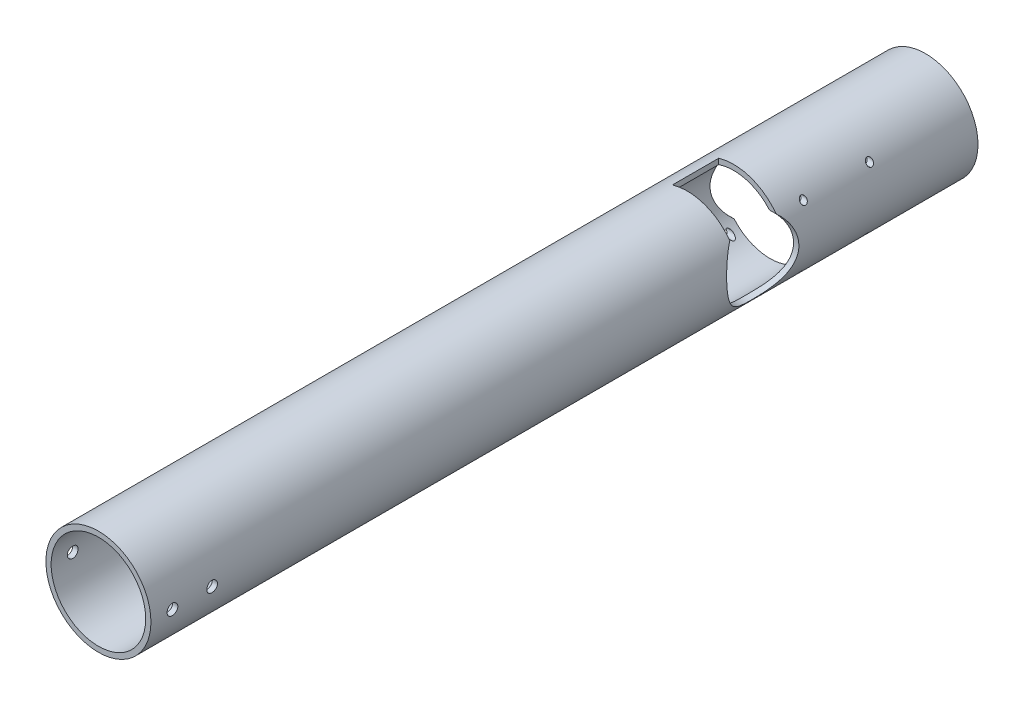
SolidWorks part; units mm, degrees
ref_plane "Front Plane" through (0, 0, 0) normal (0, 0, 1) x (1, 0, 0)
ref_plane "Top Plane" through (0, 0, 0) normal (0, 1, 0) x (1, 0, 0)
ref_plane "Right Plane" through (0, 0, 0) normal (1, 0, 0) x (0, 0, -1)
sketch "Sketch1" plane through (0, 0, 0) normal (0, 0, 1) x (1, 0, 0)
  circle A0 centre (0, 0) radius 31.75
  circle A1 centre (0, 0) radius 28.575
  dimension "D1" = 63.5
  dimension "D2" = 57.15
extrude "Boss-Extrude1" add sketch "Sketch1" along normal blind 250 and the other way blind 250 contours A1 | A0 region at (0, 0, 0)
sketch "Sketch2" plane through (0, 0, 0) normal (1, 0, 0) x (0, 0, -1)
  circle A2 centre (170, -2) radius 21.75
  dimension "D1" = 43.5
  dimension "D2" = 170
  dimension "D3" = 2
extrude "Cut-Extrude1" cut sketch "Sketch2" against normal through all
sketch "Sketch3" plane through (0, 0, 0) normal (1, 0, 0) x (0, 0, -1)
  circle A1 centre (120, 2) radius 21.75
  dimension "D1" = 120
  dimension "D2" = 43.5
  dimension "D3" = 2
extrude "Cut-Extrude2" cut sketch "Sketch3" along normal through all
sketch "Sketch5" plane through (0, 0, 0) normal (1, 0, 0) x (0, 0, -1)
  line L1 (184, -12.75) -> (156, -12.75)
  line L2 (184, -12.75) -> (184, -34.75)
  line L3 (184, -34.75) -> (156, -34.75)
  line L4 (156, -12.75) -> (156, -34.75)
  line L5 (184, -12.75) -> (156, -34.75) construction
  line L6 (184, -34.75) -> (156, -12.75) construction
  circle A0 centre (170, -2) radius 21.75 construction
  circle A1 centre (170, -2) radius 21.75 construction
  point P0 (170, -23.75)
  dimension "D1" = 28
  dimension "D2" = 22
  dimension "D3" = 170
extrude "Cut-Extrude4" cut sketch "Sketch5" against normal through all from offset 9
sketch "Sketch6" plane through (0, 0, 0) normal (1, 0, 0) x (0, 0, -1)
  line L1 (106, 34.75) -> (134, 34.75)
  line L2 (106, 34.75) -> (106, 12.75)
  line L3 (106, 12.75) -> (134, 12.75)
  line L4 (134, 34.75) -> (134, 12.75)
  line L5 (106, 34.75) -> (134, 12.75) construction
  line L6 (106, 12.75) -> (134, 34.75) construction
  circle A0 centre (120, 2) radius 21.75 construction
  circle A1 centre (120, 2) radius 21.75 construction
  point P0 (120, 23.75)
  dimension "D1" = 28
  dimension "D2" = 22
  dimension "D3" = 120
extrude "Cut-Extrude5" cut sketch "Sketch6" along normal through all from offset 9 offset against normal yes
sketch "Sketch10" plane through (0, 0, 0) normal (1, 0, 0) x (0, 0, -1)
  line L1 (210, 38) -> (130, 38)
  line L2 (210, 38) -> (210, -42)
  line L3 (210, -42) -> (130, -42)
  line L4 (130, 38) -> (130, -42)
  line L5 (210, 38) -> (130, -42) construction
  line L6 (210, -42) -> (130, 38) construction
  point P0 (170, -2)
  dimension "D1" = 80
  dimension "D2" = 80
sketch "Sketch11" plane through (0, 0, 0) normal (1, 0, 0) x (0, 0, -1)
  line L0 (210, 38) -> (130, -42) construction
  line L1 (210, -42) -> (130, 38) construction
  circle A0 centre (190, 18) radius 2
  circle A1 centre (150, 18) radius 2
  circle A2 centre (150, -22) radius 2
  circle A3 centre (190, -22) radius 2
  dimension "D5" = 4
  dimension "D6" = 4
  dimension "D7" = 4
  dimension "D8" = 4
  dimension "D1" = 20
  dimension "D2" = 20
  dimension "D3" = 20
  dimension "D4" = 20
extrude "Cut-Extrude8" cut sketch "Sketch11" against normal through all both and the other way through all
sketch "Sketch12" plane through (0, 0, 0) normal (1, 0, 0) x (0, 0, -1)
  line L1 (-250, 31.75) -> (-250, -31.75) construction
  circle A0 centre (-213, 0) radius 3.25
  circle A1 centre (-237, 0) radius 3.25
  dimension "D1" = 6.5
  dimension "D2" = 6.5
  dimension "D3" = 24
  dimension "D4" = 13
extrude "Cut-Extrude10" cut sketch "Sketch12" against normal through all both and the other way through all
